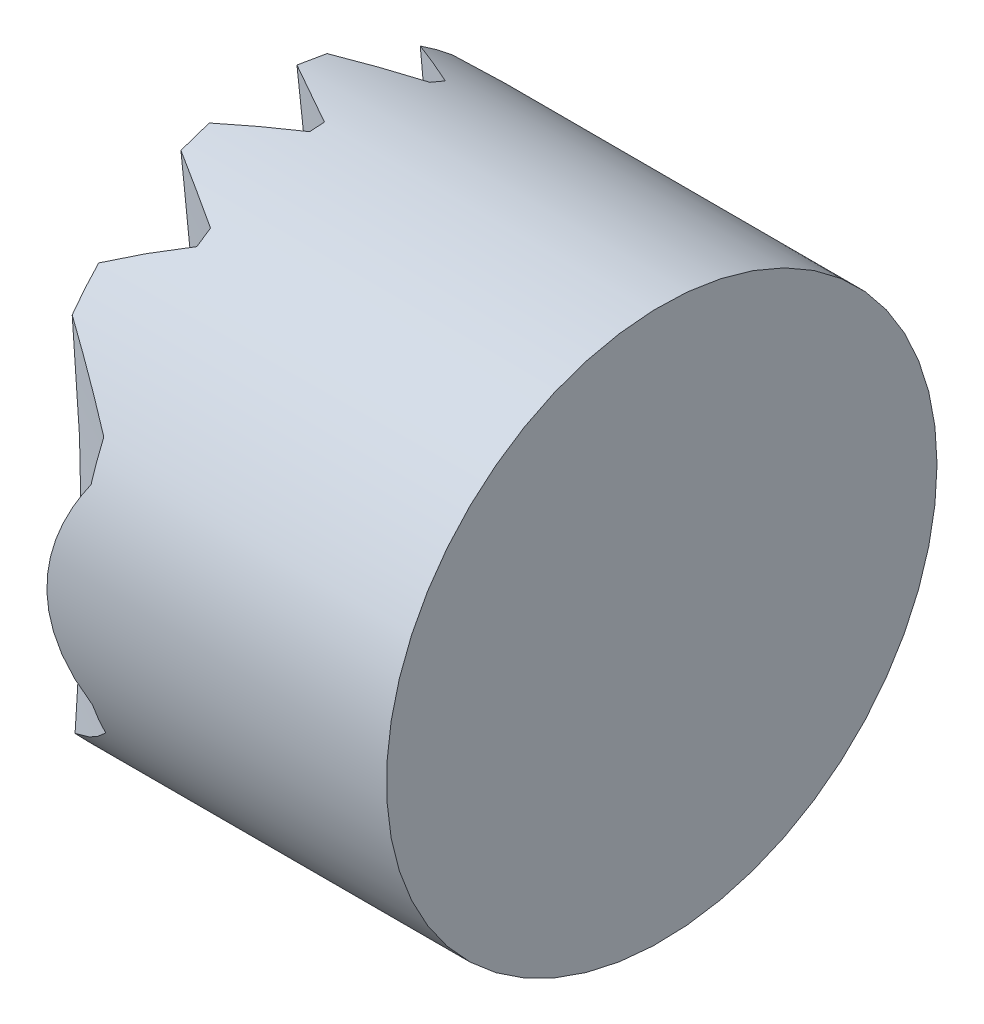
SolidWorks part; units mm, degrees
ref_plane "Alzado" through (0, 0, 0) normal (0, 0, 1) x (1, 0, 0)
ref_plane "Planta" through (0, 0, 0) normal (0, 1, 0) x (1, 0, 0)
ref_plane "Vista lateral" through (0, 0, 0) normal (1, 0, 0) x (0, 0, -1)
sketch "Croquis1" plane through (0, 0, 0) normal (0, 0, 1) x (1, 0, 0)
  circle A0 centre (0, 0) radius 26.25
  circle A1 centre (0, 0) radius 31.5
  dimension "D1" = 52.5
  dimension "D2" = 63
extrude "Saliente-Extruir1" add sketch "Croquis1" along normal blind 30
thread "Rosca1" pitch 1.5 method cut profile "Perfil de rosca1" start angle 0, offset 0, length 70, pitch 1.5, diameter 52.5
ref_plane "Plano1" through (-26.25, 0, 30) normal (0, -1, 0) x (-1, 0, 0)
sketch "Perfil de rosca1" plane through (-26.25, 0, 30) normal (0, -1, 0) x (-1, 0, 0)
  line L0 (0, 0) -> (0, 1.5) construction
  line L1 (0, 0) -> (0.8119, 0.4687)
  line L2 (0.8119, 0.4687) -> (0.8119, 0.6562)
  line L3 (0.8119, 0.6562) -> (0, 1.125)
  line L4 (0.8119, 0.5625) -> (0, 0.5625) construction
  line L11 (0, 0) -> (0, 1.125)
  point P2 (0, 0)
  dimension "Pitch" = 1.5
  dimension "Profile_Angle" = 60
  dimension "Profile_Land" = 0.1875
  dimension "Profile_Height" = 0.8119
ref_plane "Plano2" through (31.5, 0, 0) normal (1, 0, 0) x (0, 0, -1)
sketch "Croquis4" plane through (31.5, 0, 0) normal (1, 0, 0) x (0, 0, -1)
  line L0 (-15, 31.5) -> (-15, 25.3086) construction
  line L1 (0, 31.5) -> (-30, 31.5) construction
  line L2 (0, 0) -> (-4.6368, 0) construction
  line L3 (0, -31.5) -> (0, 31.5) construction
  circle A2 centre (-15, 0) radius 3.5
  circle A3 centre (-15, 0) radius 50.693
  dimension "D1" = 7
extrude "Cortar-Extruir1" cut sketch "Croquis4" against normal through all both and the other way through all
sketch "Croquis5" plane through (31.5, 0, 0) normal (1, 0, 0) x (0, 0, -1)
  circle A0 centre (-15, 0) radius 10.157
sketch "Croquis12" plane through (0, 0, 0) normal (0, 0, 1) x (1, 0, 0)
  line L1 (-10.3231, -10.9552) -> (-34.7615, -10.9552)
  line L2 (-10.3231, -10.9552) -> (-10.3231, 9.2697)
  line L3 (-10.3231, 9.2697) -> (-34.7615, 9.2697)
  line L4 (-34.7615, -10.9552) -> (-34.7615, 9.2697)
extrude "Cortar-Extruir7" cut sketch "Croquis12" along normal through all
sketch "Croquis6" plane through (31.5, 0, 0) normal (1, 0, 0) x (0, 0, -1)
  circle A0 centre (-15, 0) radius 4
  dimension "D1" = 8
extrude "Saliente-Extruir2" add sketch "Croquis6" against normal up to surface
sketch "Croquis9" plane through (0, 0, 0) normal (1, 0, 0) x (0, 0, -1)
  circle A0 centre (-15.3606, 0) radius 28.0562
sketch "Croquis10" plane through (0, 0, 0) normal (1, 0, 0) x (0, 0, -1)
  circle A0 centre (-15, 0) radius 3
  circle A1 centre (-15, 0) radius 4
extrude "Cortar-Extruir3" [suppressed] cut sketch "Croquis10" along normal through all
sketch "Croquis11" plane through (31.5, 0, 0) normal (1, 0, 0) x (0, 0, -1)
  line L0 (-18.5, 0) -> (-11.5, 0) construction
  circle A0 centre (-15, 0) radius 10.3659
extrude "Cortar-Extruir5" cut sketch "Croquis11" against normal blind 0.5
